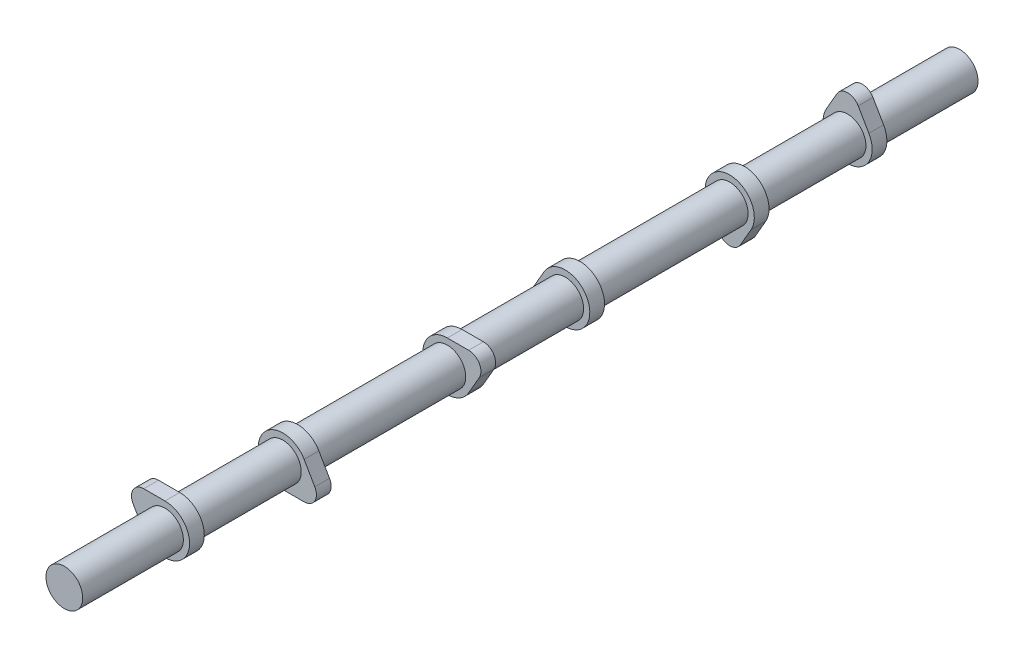
SolidWorks part; units mm, degrees
material "Plain Carbon Steel"
ref_plane "Front Plane" through (0, 0, 0) normal (0, 0, 1) x (1, 0, 0)
ref_plane "Top Plane" through (0, 0, 0) normal (0, 1, 0) x (1, 0, 0)
ref_plane "Right Plane" through (0, 0, 0) normal (1, 0, 0) x (0, 0, -1)
sketch "Sketch2" plane through (0, 0, 0) normal (0, 0, 1) x (1, 0, 0)
  line L0 (-10.9985, 6.35) -> (-5.4993, 15.875)
  line L1 (10.9985, 6.35) -> (5.4993, 15.875)
  arc A0 (-10.9985, 6.35) -> (10.9985, 6.35) centre (0, 0) ccw
  arc A1 (5.4993, 15.875) -> (-5.4993, 15.875) centre (0, 12.7) ccw
  dimension "D1" = 25.4
  dimension "D2" = 12.7
extrude "Boss-Extrude1" add sketch "Sketch2" along normal blind 7.62
ref_axis "Axis1" through (0, 0, 399.5939) along (0, 0, -1)
move or copy body "Body-Move/Copy4" bodies to move or copy 101 copy yes number of copies 1 translate (0, 0, 60.96)
move or copy body "Body-Move/Copy5" bodies to move or copy 105 copy no rotation origin (0, 0, 0) rotation axis (0, 0, 1) rotation angle 180
sketch "Sketch4" plane through (0, 0, 0) normal (0, 0, 1) x (1, 0, 0)
  circle A0 centre (0, 0) radius 9.5
  dimension "D1" = 19
extrude "Boss-Extrude2" add sketch "Sketch4" along normal blind 146.05 from offset 25.4 offset against normal yes
pattern_linear "LPattern2" count 3 spacing 146.05 along (0, 0, 1) of bodies 107
move or copy body "Body-Move/Copy6" bodies to move or copy 109 copy no rotation origin (0, 0, 0) rotation axis (0, 0, 1) rotation angle 120
move or copy body "Body-Move/Copy7" bodies to move or copy 110 copy no rotation origin (0, 0, 0) rotation axis (0, 0, -1) rotation angle 120
sketch "Sketch6" plane through (0, 0, -25.4) normal (0, 0, -1) x (-1, 0, 0)
  circle A1 centre (0, 0) radius 9.5
  circle A2 centre (0, 0) radius 9.5
  dimension "D1" = 0
extrude "Boss-Extrude3" add sketch "Sketch6" along normal blind 24.94
combine bodies "Combine1" operation type add bodies to combine 113 111 112
